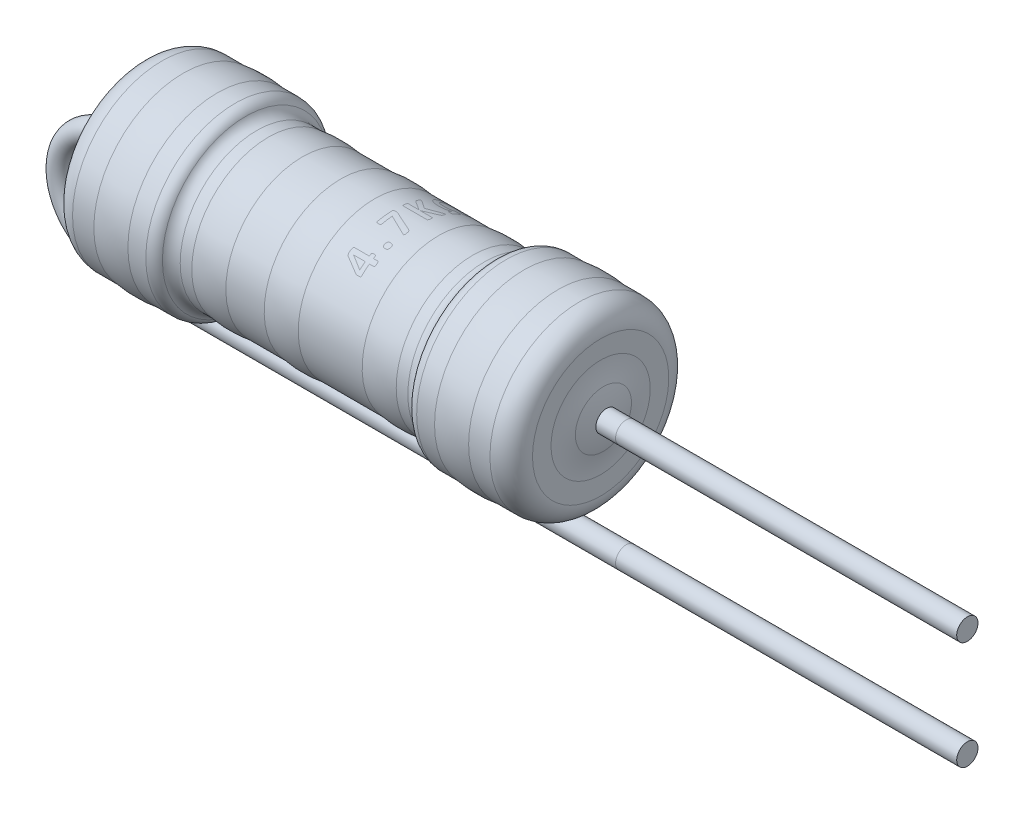
SolidWorks part; units mm, degrees
ref_plane "Front Plane" through (0, 0, 0) normal (0, 0, 1) x (1, 0, 0)
ref_plane "Top Plane" through (0, 0, 0) normal (0, 1, 0) x (1, 0, 0)
ref_plane "Right Plane" through (0, 0, 0) normal (1, 0, 0) x (0, 0, -1)
sketch "Sketch Set Wire Width" plane through (0, 0, 0) normal (0, 0, 1) x (1, 0, 0)
  line L0 (0, 0) -> (6, 0)
  line L1 (6, -2.54) -> (-6, -2.54)
  line L2 (6, 0) -> (14.0102, 0)
  line L3 (-6, 0) -> (-6, -2.54) construction
  line L4 (-6, 0) -> (-6, -2.54) construction
  line L5 (6, -2.54) -> (6, 0) construction
  line L6 (6, -2.54) -> (14.0102, -2.54)
  line L7 (14.0102, -2.54) -> (14.0102, 0) construction
  line L8 (-6, 0) -> (0, 0)
  arc A0 (-6, 0) -> (-6, -2.54) centre (-6, -1.27) ccw
  dimension "D2" = 2.54
  dimension "D3" = 30
  dimension "D1" = 12
  dimension "D4" = 6
sketch "Sketch Wire Diameter" plane through (0, 0, 0) normal (1, 0, 0) x (0, 0, -1)
  circle A0 centre (0, 0) radius 0.25
  dimension "D1" = 0.5
sweep "SET WIRE LENGTH" add profiles "Sketch Wire Diameter" path "Sketch Set Wire Width"
sketch "Sketch3" plane through (0, 0, 0) normal (0, 0, 1) x (1, 0, 0)
  line L0 (-5.4, 0) -> (5.4, 0)
  line L1 (0, 0) -> (0, 1.8) construction
  line L2 (-2.9, 1.8) -> (2.9, 1.8)
  line L3 (-5.4, 0) -> (-5.4, 1.6)
  line L4 (-4.9, 2.1) -> (-3.18, 2.1)
  line L5 (-2.9, 1.82) -> (-2.9, 1.8)
  line L6 (5.4, 0) -> (5.4, 1.6)
  line L7 (4.9, 2.1) -> (3.18, 2.1)
  line L8 (2.9, 1.82) -> (2.9, 1.8)
  arc A0 (-5.4, 1.6) -> (-4.9, 2.1) centre (-4.9, 1.6) cw
  arc A1 (5.4, 1.6) -> (4.9, 2.1) centre (4.9, 1.6) ccw
  arc A2 (-3.18, 2.1) -> (-2.9, 1.82) centre (-3.18, 1.82) cw
  arc A3 (3.18, 2.1) -> (2.9, 1.82) centre (3.18, 1.82) ccw
  dimension "D5" = 0.5
  dimension "D6" = 0.28
  dimension "D1" = 10.8
  dimension "D2" = 5.8
  dimension "D3" = 1.8
  dimension "D4" = 2.1
revolve "Revolve2" add sketch "Sketch3" angle 360 about L0
fillet "Fillet1" radius 0.3 2 edges at (2.9, 0, 1.8) (-2.9, 0, 1.8)
sketch "Sketch5" plane through (0, 0, 0) normal (0, 0, 1) x (1, 0, 0)
  line L0 (0, 0) -> (2, 0) construction
  line L1 (0, 0) -> (-0.3, 0) construction
  line L2 (-0.3, 0) -> (-2, 0) construction
  line L3 (-2, 0) -> (-4, 0) construction
  line L4 (2, 0) -> (4, 0) construction
  line L5 (-4, 0) -> (-4, 2.1) construction
  line L6 (-0.3, 0) -> (-0.3, 1.8) construction
  line L7 (-2, 0) -> (-2, 1.8) construction
  line L8 (2, 0) -> (2, 1.8) construction
  line L9 (4, 0) -> (4, 2.1) construction
  line L10 (-4, 2.1) -> (-4, 2.13) construction
  line L11 (-4.9, 2.1) -> (-3.18, 2.1) construction
  line L12 (4.9, 2.1) -> (3.18, 2.1) construction
  line L13 (-2.9, 1.8) -> (2.9, 1.8) construction
  line L14 (-2, 1.8) -> (-2, 1.83) construction
  line L17 (-4.4, 2.1) -> (-3.6, 2.1)
  line L19 (-5.4, 0) -> (5.4, 0) construction
  line L22 (-2.4, 1.8) -> (-1.6, 1.8) construction
  line L26 (-0.7, 1.8) -> (0.1, 1.8) construction
  line L30 (1.6, 1.8) -> (2.4, 1.8) construction
  line L34 (3.6, 2.1) -> (4.4, 2.1) construction
  line L36 (-0.3, 1.8) -> (-0.3, 1.83) construction
  line L37 (2, 1.8) -> (2, 1.83) construction
  line L38 (4, 2.1) -> (4, 2.13) construction
  arc A0 (-4.4, 2.1) -> (-3.6, 2.1) centre (-4, -0.5517) cw
  arc A1 (-2.4, 1.8) -> (-1.6, 1.8) centre (-2, -0.8517) cw construction
  arc A2 (-0.7, 1.8) -> (0.1, 1.8) centre (-0.3, -0.8517) cw construction
  arc A3 (1.6, 1.8) -> (2.4, 1.8) centre (2, -0.8517) cw construction
  arc A4 (3.6, 2.1) -> (4.4, 2.1) centre (4, -0.5517) cw construction
  dimension "D3" = 0.8
  dimension "D1" = 4
  dimension "D2" = 4
  dimension "D4" = 0.03
  dimension "D5" = 2
  dimension "D6" = 2
  dimension "D7" = 1.7
revolve "Band 1" add sketch "Sketch5" angle 360 about L2
sketch "Sketch8" plane through (0, 0, 0) normal (0, 0, 1) x (1, 0, 0)
  line L0 (-2.4, 1.8) -> (-1.6, 1.8) construction
  line L1 (-2.4, 1.8) -> (-1.6, 1.8)
  arc A0 (-1.6, 1.8) -> (-2.4, 1.8) centre (-2, -0.8517) ccw construction
  arc A1 (-1.6, 1.8) -> (-2.4, 1.8) centre (-2, -0.8517) ccw
revolve "Band 2" add sketch "Sketch8" angle 360 about L2
sketch "Sketch9" plane through (0, 0, 0) normal (0, 0, 1) x (1, 0, 0)
  line L0 (-0.7, 1.8) -> (0.1, 1.8) construction
  line L1 (-0.7, 1.8) -> (0.1, 1.8)
  arc A0 (0.1, 1.8) -> (-0.7, 1.8) centre (-0.3, -0.8517) ccw construction
  arc A1 (0.1, 1.8) -> (-0.7, 1.8) centre (-0.3, -0.8517) ccw
revolve "Band 3" add sketch "Sketch9" angle 360 about L2
sketch "Sketch10" plane through (0, 0, 0) normal (0, 0, 1) x (1, 0, 0)
  line L0 (1.6, 1.8) -> (2.4, 1.8) construction
  line L1 (1.6, 1.8) -> (2.4, 1.8)
  arc A0 (2.4, 1.8) -> (1.6, 1.8) centre (2, -0.8517) ccw construction
  arc A1 (2.4, 1.8) -> (1.6, 1.8) centre (2, -0.8517) ccw
revolve "Band 4" add sketch "Sketch10" angle 360 about L0
sketch "Sketch11" plane through (0, 0, 0) normal (0, 0, 1) x (1, 0, 0)
  line L0 (3.6, 2.1) -> (4.4, 2.1) construction
  line L1 (3.6, 2.1) -> (4.4, 2.1)
  arc A0 (4.4, 2.1) -> (3.6, 2.1) centre (4, -0.5517) ccw construction
  arc A1 (4.4, 2.1) -> (3.6, 2.1) centre (4, -0.5517) ccw
revolve "Band 5" add sketch "Sketch11" angle 360 about L4
sketch "Sketch12" plane through (0, 0, 0) normal (0, 0, 1) x (1, 0, 0)
  line L0 (-5.35, 0) -> (5.35, 0) construction
  line L1 (-5.35, 1) -> (-5.35, 0)
  line L2 (5.35, 1) -> (5.35, 0)
  line L3 (-5.35, 0) -> (-5.55, 0)
  line L4 (5.35, 0) -> (5.55, 0)
  arc A0 (-5.35, 1) -> (-5.55, 0) centre (-2.95, 0) ccw
  arc A1 (5.35, 1) -> (5.55, 0) centre (2.95, 0) cw
  dimension "D3" = 0.2
  dimension "D4" = 2.6
  dimension "D1" = 10.7
  dimension "D2" = 1
revolve "Revolve10" add sketch "Sketch12" angle 360 about L0
fillet "Fillet2" radius 2 2 edges at (5.4, 0, 0.8703) (-5.4, 0, -0.8703)
ref_plane "Plane2" through (0, 3, 0) normal (0, 1, 0) x (1, 0, 0)
sketch "Sketch13" plane through (0, 3, 0) normal (0, 1, 0) x (1, 0, 0)
  line L0 (0, 0) -> (1.15, 0) construction
  line L1 (1.15, 1.75) -> (1.15, -1.75) construction
  text T0 "4.7KΩ" font "Calibri" height 0.6
  dimension "D1" = 3.5
  dimension "D2" = 1.15
wrap "Wrap1" sketch "Sketch13" wrap type scribe source sketch "Sketch13" face at (0.1, 1.8, 0)
